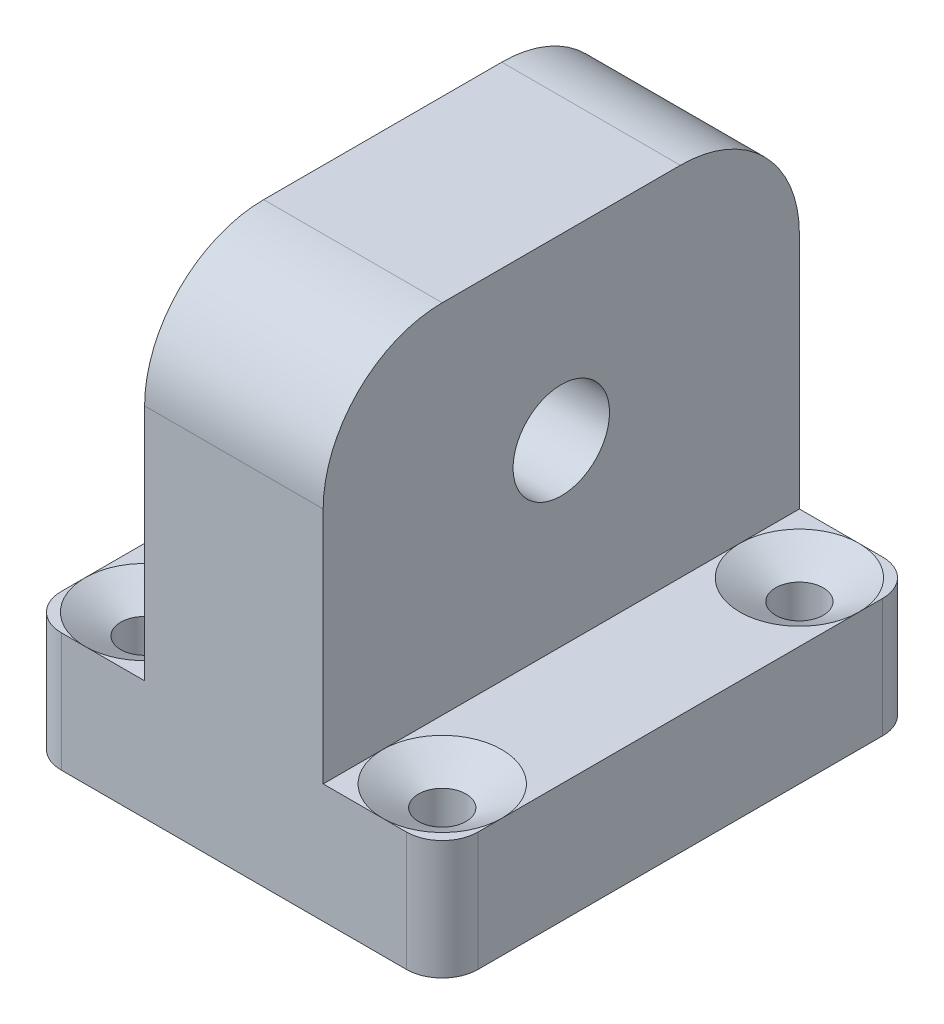
SolidWorks part; units mm, degrees
ref_plane "前视基准面" through (0, 0, 0) normal (0, 0, 1) x (1, 0, 0)
ref_plane "上视基准面" through (0, 0, 0) normal (0, 1, 0) x (1, 0, 0)
ref_plane "右视基准面" through (0, 0, 0) normal (1, 0, 0) x (0, 0, -1)
sketch "草图2" plane through (0, 0, 0) normal (0, 1, 0) x (1, 0, 0)
  line L1 (-17.5, 20) -> (17.5, 20)
  line L2 (-17.5, 20) -> (-17.5, -20)
  line L3 (-17.5, -20) -> (17.5, -20)
  line L4 (17.5, 20) -> (17.5, -20)
  line L5 (-17.5, 20) -> (17.5, -20) construction
  line L6 (-17.5, -20) -> (17.5, 20) construction
  point P0 (0, 0)
  dimension "D1" = 40
  dimension "D2" = 35
extrude "凸台-拉伸1" add sketch "草图2" along normal blind 10
sketch "草图3" plane through (0, 10, 0) normal (0, 1, 0) x (1, 0, 0)
  line L1 (-12.5, 15) -> (12.5, 15)
  line L2 (-12.5, 15) -> (-12.5, -15)
  line L3 (-12.5, -15) -> (12.5, -15)
  line L4 (12.5, 15) -> (12.5, -15)
  line L5 (-12.5, 15) -> (12.5, -15) construction
  line L6 (-12.5, -15) -> (12.5, 15) construction
  circle A0 centre (12.5, 15) radius 2
  circle A1 centre (-12.5, 15) radius 2
  circle A2 centre (-12.5, -15) radius 2
  circle A3 centre (12.5, -15) radius 2
  point P0 (0, 0)
  dimension "D3" = 4
  dimension "D4" = 4
  dimension "D5" = 4
  dimension "D6" = 4
  dimension "D1" = 30
  dimension "D2" = 25
extrude "切除-拉伸2" cut sketch "草图3" against normal blind 10 contours A1 | A2 | A3 | A0
sketch "草图4" plane through (0, 10, 0) normal (0, 1, 0) x (1, 0, 0)
  line L0 (-17.5, -20) -> (17.5, -20) construction
  line L1 (-7.5, 20) -> (7.5, 20)
  line L2 (-7.5, 20) -> (-7.5, -20)
  line L3 (-7.5, -20) -> (7.5, -20)
  line L4 (7.5, 20) -> (7.5, -20)
  line L5 (-7.5, 20) -> (7.5, -20) construction
  line L6 (-7.5, -20) -> (7.5, 20) construction
  point P0 (0, 0)
  dimension "D1" = 15
extrude "凸台-拉伸2" add sketch "草图4" along normal blind 30
sketch "草图5" plane through (7.5, 0, 0) normal (1, 0, 0) x (0, 0, -1)
  line L4 (-20, 40) -> (-20, 10) construction
  line L5 (-20, 10) -> (20, 10) construction
  circle A0 centre (0, 25) radius 7
  dimension "D1" = 20
  dimension "D2" = 14
  dimension "D3" = 15
extrude "切除-拉伸3" cut sketch "草图5" against normal through all
fillet "圆角2" radius 3 4 edges at (17.5, 5, -20) (-17.5, 5, -20) (-17.5, 5, 20) (17.5, 5, 20)
fillet "圆角3" radius 10 2 edges at (0, 40, 20) (0, 40, -20)
chamfer "倒角1" distance 3 angle 30 4 edges at (12.5, 10, -13) (12.5, 10, 17) (-12.5, 10, -13) (-12.5, 10, 17) first distance on face at (13.3738, 10, 3.3333) first distance on face at (-13.3738, 10, -3.3333)
sketch "草图6" plane through (7.5, 0, 0) normal (1, 0, 0) x (0, 0, -1)
  line L2 (-15, 10) -> (15, 10) construction
  line L3 (20, 30) -> (20, 10) construction
  circle A0 centre (0, 25) radius 4.05
  circle A1 centre (0, 25) radius 7
  dimension "D3" = 8.1
  dimension "D1" = 15
  dimension "D2" = 20
extrude "凸台-拉伸3" add sketch "草图6" against normal blind 10
